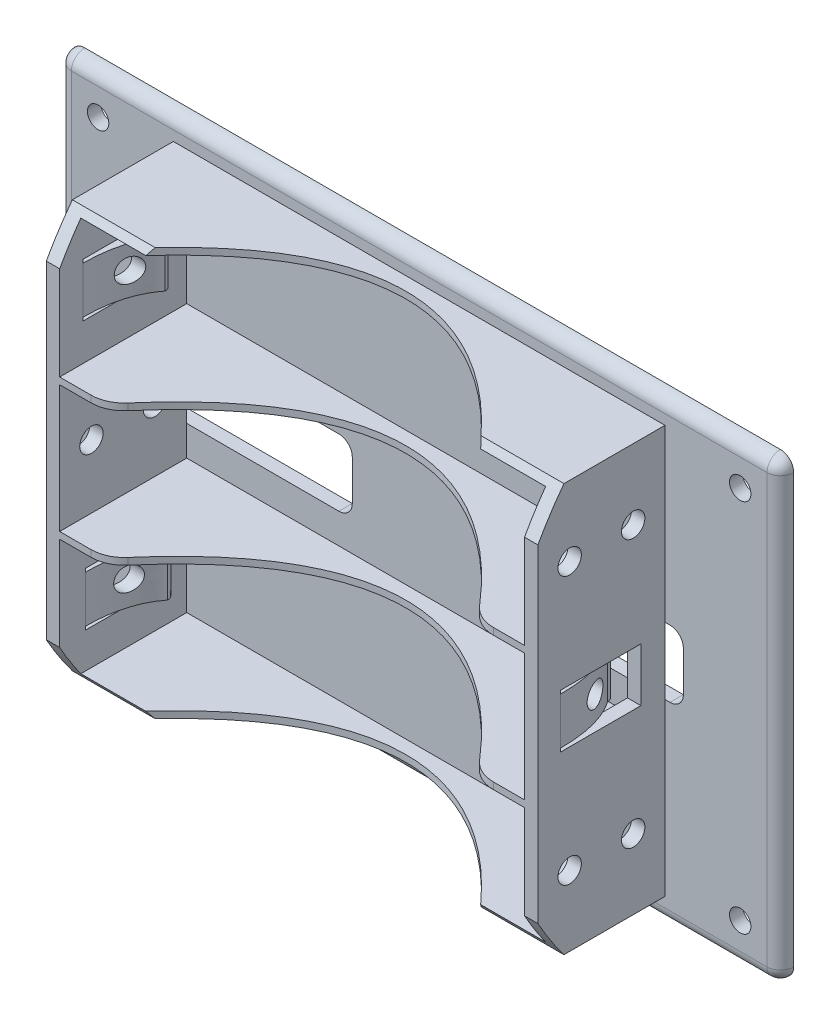
SolidWorks part; units mm, degrees
ref_plane "Płaszczyzna przednia" through (0, 0, 0) normal (0, 0, 1) x (1, 0, 0)
ref_plane "Płaszczyzna górna" through (0, 0, 0) normal (0, 1, 0) x (1, 0, 0)
ref_plane "Płaszczyzna prawa" through (0, 0, 0) normal (1, 0, 0) x (0, 0, -1)
sketch "Szkic1" plane through (0, 0, 0) normal (0, 0, 1) x (1, 0, 0)
  line L0 (-32.266, 2.8412) -> (-32.266, 0.8412) construction
  line L1 (-32.266, 0.8412) -> (-34.266, 0.8412) construction
  line L2 (71.734, 66.8412) -> (71.734, 68.8412) construction
  line L3 (71.734, 68.8412) -> (73.734, 68.8412) construction
  line L5 (73.734, 68.8412) -> (-34.266, 68.8412)
  line L6 (73.734, 68.8412) -> (73.734, 0.8412)
  line L7 (73.734, 0.8412) -> (-34.266, 0.8412)
  line L8 (-34.266, 68.8412) -> (-34.266, 0.8412)
extrude "Dodanie-wyciągnięcie1" add sketch "Szkic1" along normal blind 2
sketch "Szkic2" plane through (0, 0, 2) normal (0, 0, 1) x (1, 0, 0)
  line L0 (-34.266, 34.8412) -> (-15.016, 34.8412) construction
  line L1 (-34.266, 68.8412) -> (-34.266, 0.8412) construction
  line L2 (-15.016, 34.8412) -> (54.484, 34.8412) construction
  line L3 (54.484, 34.8412) -> (73.734, 34.8412) construction
  line L4 (73.734, 0.8412) -> (73.734, 68.8412) construction
  line L5 (-15.016, 34.8412) -> (-15.016, 25.3412)
  line L6 (-15.016, 25.3412) -> (-15.016, 24.3412)
  line L7 (-15.016, 24.3412) -> (-15.016, 5.3412)
  line L8 (-15.016, 5.3412) -> (-15.016, 4.3412)
  line L9 (-15.016, 34.8412) -> (-15.016, 44.3412)
  line L10 (-15.016, 44.3412) -> (-15.016, 45.3412)
  line L11 (-15.016, 45.3412) -> (-15.016, 64.3412)
  line L12 (54.484, 34.8412) -> (54.484, 44.3412)
  line L13 (-15.016, 64.3412) -> (-15.016, 65.3412)
  line L14 (54.484, 44.3412) -> (54.484, 45.3412)
  line L15 (54.484, 45.3412) -> (54.484, 64.3412)
  line L16 (54.484, 64.3412) -> (54.484, 65.3412)
  line L17 (54.484, 34.8412) -> (54.484, 25.3412)
  line L18 (54.484, 25.3412) -> (54.484, 24.3412)
  line L19 (54.484, 24.3412) -> (54.484, 5.3412)
  line L20 (54.484, 5.3412) -> (54.484, 4.3412)
  line L21 (-15.016, 25.3412) -> (54.484, 25.3412)
  line L22 (54.484, 44.3412) -> (-15.016, 44.3412)
  line L23 (-15.016, 24.3412) -> (54.484, 24.3412)
  line L24 (-15.016, 5.3412) -> (54.484, 5.3412)
  line L25 (-15.016, 45.3412) -> (54.484, 45.3412)
  line L26 (-15.016, 64.3412) -> (54.484, 64.3412)
  line L27 (-15.016, 65.3412) -> (54.484, 65.3412)
  line L28 (-15.016, 4.3412) -> (54.484, 4.3412)
  line L29 (-15.016, 4.3412) -> (-17.016, 4.3412)
  line L30 (-17.016, 4.3412) -> (-17.016, 65.3412)
  line L31 (-17.016, 65.3412) -> (-15.016, 65.3412)
  line L32 (54.484, 4.3412) -> (56.484, 4.3412)
  line L33 (56.484, 4.3412) -> (56.484, 65.3412)
  line L34 (56.484, 65.3412) -> (54.484, 65.3412)
  dimension "D1" = 61
  dimension "D2" = 2
  dimension "D3" = 2
  dimension "D4" = 61
extrude "Dodanie-wyciągnięcie2" add sketch "Szkic2" along normal blind 19 contours L31 L30 L29 L8 L7 L6 L5 L9 L10 L11 L13 | L33 L34 L16 L15 L14 L12 L17 L18 L19 L20 L32 | L25 L10 L22 L14 | L27 L13 L26 L16 | L6 L23 L18 L21 | L8 L28 L20 L24
sketch "Szkic4" plane through (-15.016, 0, 0) normal (1, 0, 0) x (0, 0, -1)
  line L0 (-2, 23.9412) -> (-20.2, 24.3412) construction
  line L1 (-2, 24.3412) -> (-2, 5.3412) construction
  line L2 (-21, 24.3412) -> (-2, 24.3412) construction
  line L4 (-2, 64.3412) -> (-21, 64.3412) construction
  line L5 (-21, 64.3412) -> (-2, 64.3412) construction
  line L6 (-2, 64.3412) -> (-2, 45.3412) construction
  line L7 (-20.2, 24.3412) -> (-20.2, 5.3412) construction
  line L8 (-21, 5.3412) -> (-2, 5.3412) construction
  line L9 (-21, 64.3412) -> (-21, 45.3412) construction
  line L10 (-21, 45.3412) -> (-2, 45.3412) construction
  line L11 (-21, 45.3412) -> (-2, 64.3412) construction
  line L12 (-20.2, 5.3412) -> (-2, 23.9412) construction
  line L14 (-5.5, 50.8412) -> (-17.5, 50.8412)
  line L15 (-5.5, 50.8412) -> (-5.5, 58.8412)
  line L16 (-5.5, 58.8412) -> (-17.5, 58.8412)
  line L17 (-17.5, 50.8412) -> (-17.5, 58.8412)
  line L18 (-5.5, 50.8412) -> (-17.5, 58.8412) construction
  line L19 (-5.5, 58.8412) -> (-17.5, 50.8412) construction
  line L20 (-5.1, 10.6412) -> (-17.1, 10.6412)
  line L21 (-5.1, 10.6412) -> (-5.1, 18.6412)
  line L22 (-5.1, 18.6412) -> (-17.1, 18.6412)
  line L23 (-17.1, 10.6412) -> (-17.1, 18.6412)
  line L24 (-5.1, 10.6412) -> (-17.1, 18.6412) construction
  line L25 (-5.1, 18.6412) -> (-17.1, 10.6412) construction
  point P6 (-11.5, 54.8412)
  point P23 (-11.1, 14.6412)
extrude "Wytnij-wyciągnięcie1" cut sketch "Szkic4" against normal blind 2
sketch "Szkic5" plane through (54.484, 0, 0) normal (-1, 0, 0) x (0, 0, 1)
  line L0 (2, 44.3412) -> (21.2, 44.3412) construction
  line L1 (21, 44.3412) -> (2, 44.3412) construction
  line L2 (2, 25.3412) -> (2, 44.3412) construction
  line L3 (21.2, 44.3412) -> (21.2, 25.3412) construction
  line L4 (21, 25.3412) -> (2, 25.3412) construction
  line L5 (21.2, 25.3412) -> (2, 44.3412) construction
  line L7 (5.6, 30.8412) -> (17.6, 30.8412)
  line L8 (5.6, 30.8412) -> (5.6, 38.8412)
  line L9 (5.6, 38.8412) -> (17.6, 38.8412)
  line L10 (17.6, 30.8412) -> (17.6, 38.8412)
  line L11 (5.6, 30.8412) -> (17.6, 38.8412) construction
  line L12 (5.6, 38.8412) -> (17.6, 30.8412) construction
  point P6 (11.6, 34.8412)
extrude "Wytnij-wyciągnięcie2" cut sketch "Szkic5" against normal blind 2
sketch "Szkic6" plane through (0, 58.8412, 0) normal (0, -1, 0) x (1, 0, 0)
  line L0 (-15.016, 5.5) -> (-14.516, 5.5) construction
  line L1 (-17.016, 5.5) -> (-15.016, 5.5) construction
  line L2 (-15.016, 5.5) -> (-15.016, 17.5) construction
  line L3 (-14.516, 5.5) -> (-14.516, 8) construction
  line L4 (-17.016, 11.5) -> (-15.016, 11.5) construction
  line L5 (-17.016, 5.5) -> (-17.016, 17.5) construction
  line L6 (-14.516, 8) -> (-12.266, 8)
  line L8 (-17.016, 17.5) -> (-15.016, 17.5) construction
  line L9 (-17.016, 17.5) -> (-17.016, 11.5) construction
  line L10 (-17.016, 11.5) -> (-14.516, 8) construction
  line L11 (-15.016, 17.5) -> (-15.016, 11.5) construction
  line L12 (-15.016, 11.5) -> (-12.266, 8) construction
  line L13 (-15.016, 17.5) -> (-17.016, 17.5)
  circle A0 centre (-13.391, 8) radius 1.125
  spline S0 degree 2 poles (-17.016, 17.5) (-17.016, 11.5) (-14.516, 8) knots 0 0 0 1 1 1
  spline S1 degree 2 poles (-15.016, 17.5) (-15.016, 11.5) (-12.266, 8) knots 0 0 0 1 1 1
  line M7 (-15.016, 5.5) -> (-15.016, 17.5)
  line M8 (-15.016, 17.5) -> (-17.016, 17.5)
  dimension "D1" = 2.25
extrude "Dodanie-wyciągnięcie3" add sketch "Szkic6" along normal blind 7 from offset 0.5 contours S0 M8 M7 | S1 S0 A0 M7 | S1 A0 L6 | L6 A0
sketch "Szkic7" plane through (0, 18.6412, 0) normal (0, -1, 0) x (1, 0, 0)
  line L0 (-15.016, 5.1) -> (-14.516, 5.1) construction
  line L1 (-14.516, 5.1) -> (-14.516, 7.6) construction
  line L2 (-14.516, 7.6) -> (-12.266, 7.6)
  line L3 (-15.016, 5.1) -> (-15.016, 17.1) construction
  line L4 (-12.266, 7.6) -> (-15.016, 11.1) construction
  line L6 (-15.016, 11.1) -> (-15.016, 17.1) construction
  line L7 (-17.016, 17.1) -> (-15.016, 17.1) construction
  line L8 (-14.516, 7.6) -> (-17.016, 11.1) construction
  line L9 (-17.016, 5.1) -> (-17.016, 17.1) construction
  line L10 (-17.016, 11.1) -> (-17.016, 17.1) construction
  line L11 (-15.016, 17.1) -> (-17.016, 17.1)
  circle A0 centre (-13.391, 7.6) radius 1.125
  spline S0 degree 2 poles (-12.266, 7.6) (-15.016, 11.1) (-15.016, 17.1) knots 0 0 0 1 1 1
  spline S1 degree 2 poles (-14.516, 7.6) (-17.016, 11.1) (-17.016, 17.1) knots 0 0 0 1 1 1
  line M5 (-15.016, 5.1) -> (-15.016, 17.1)
  line M6 (-15.016, 17.1) -> (-17.016, 17.1)
  dimension "D1" = 2.25
extrude "Dodanie-wyciągnięcie4" add sketch "Szkic7" along normal blind 7 from offset 0.5 contours L2 S0 A0 | L2 A0 | S1 A0 S0 M5 | S1 M5 M6
sketch "Szkic8" plane through (0, 30.8412, 0) normal (0, 1, 0) x (1, 0, 0)
  line L0 (54.484, -5.6) -> (53.984, -5.6) construction
  line L1 (53.984, -5.6) -> (53.984, -8.1) construction
  line L2 (53.984, -8.1) -> (51.734, -8.1)
  line L3 (56.484, -5.6) -> (56.484, -17.6) construction
  line L4 (56.484, -17.6) -> (56.484, -11.6) construction
  line L6 (56.484, -11.6) -> (53.984, -8.1) construction
  line L7 (54.484, -5.6) -> (54.484, -17.6) construction
  line L8 (54.484, -17.6) -> (54.484, -11.6) construction
  line L10 (54.484, -11.6) -> (51.734, -8.1) construction
  line L11 (54.484, -17.6) -> (56.484, -17.6)
  circle A0 centre (52.859, -8.1) radius 1.125
  spline S0 degree 2 poles (56.484, -17.6) (56.484, -11.6) (53.984, -8.1) knots 0 0 0 1 1 1
  spline S1 degree 2 poles (54.484, -17.6) (54.484, -11.6) (51.734, -8.1) knots 0 0 0 1 1 1
  line M9 (54.484, -5.6) -> (54.484, -17.6)
  line M10 (54.484, -17.6) -> (56.484, -17.6)
  dimension "D1" = 2.25
extrude "Dodanie-wyciągnięcie5" add sketch "Szkic8" along normal blind 7 from offset 0.5 contours S1 S0 A0 M9 | S0 M10 M9 | S1 A0 L2 | L2 A0
sketch "Szkic9" plane through (0, 65.3412, 0) normal (0, 1, 0) x (1, 0, 0)
  line L0 (56.484, -21) -> (47.484, -21) construction
  line L1 (56.484, -21) -> (56.484, -2) construction
  line L2 (-17.016, -21) -> (56.484, -21) construction
  line L3 (47.484, -21) -> (-8.016, -21)
  line L4 (-8.016, -21) -> (-17.016, -21) construction
  line L5 (-17.016, -21) -> (-17.016, -2) construction
  line L6 (56.484, -2) -> (-17.016, -2) construction
  line L7 (19.734, -21) -> (19.734, -2) construction
  line L8 (19.734, -2) -> (19.734, 13) construction
  line L9 (-17.016, -2) -> (56.484, -2) construction
  line L11 (47.484, -21) -> (19.734, 13) construction
  line L12 (19.734, 13) -> (-8.016, -21) construction
  spline S0 degree 2 poles (47.484, -21) (19.734, 13) (-8.016, -21) knots 0 0 0 1 1 1
extrude "Wytnij-wyciągnięcie3" cut sketch "Szkic9" against normal blind 67 contours L3 S0
fillet "Zaokrąglenie2" radius 5 8 edges at (47.484, 64.8412, 21) (-8.016, 64.8412, 21) (-8.016, 44.8412, 21) (47.484, 44.8412, 21) (-8.016, 24.8412, 21) (47.484, 24.8412, 21) (-8.016, 4.8412, 21) (47.484, 4.8412, 21)
sketch "Szkic10" plane through (54.484, 0, 0) normal (-1, 0, 0) x (0, 0, 1)
  line L0 (2, 24.3412) -> (21, 5.3412) construction
  line L1 (21, 24.3412) -> (2, 24.3412) construction
  line L2 (2, 5.3412) -> (2, 24.3412) construction
  line L3 (21, 5.3412) -> (21, 24.3412) construction
  line L4 (11.5, 54.8412) -> (2, 54.8412) construction
  line L6 (2, 64.3412) -> (21, 45.3412) construction
  line L7 (21, 64.3412) -> (2, 64.3412) construction
  line L8 (2, 45.3412) -> (2, 64.3412) construction
  line L9 (21, 45.3412) -> (21, 64.3412) construction
  line L10 (11.5, 54.8412) -> (21, 54.8412) construction
  line L11 (2, 14.8412) -> (11.5, 14.8412) construction
  line L12 (11.5, 14.8412) -> (21, 14.8412) construction
  line L13 (2, 44.3412) -> (21, 25.3412) construction
  line L14 (2, 25.3412) -> (2, 44.3412) construction
  circle A0 centre (6.75, 14.8412) radius 1.75
  circle A1 centre (16.25, 14.8412) radius 1.75
  circle A2 centre (6.75, 54.8412) radius 1.75
  circle A3 centre (16.25, 54.8412) radius 1.75
  circle A4 centre (11.5, 34.8412) radius 1.75
extrude "Wytnij-wyciągnięcie5" cut sketch "Szkic10" against normal blind 10 and the other way blind 10
sketch "Szkic11" plane through (-15.016, 0, 0) normal (1, 0, 0) x (0, 0, -1)
  line L0 (-21, 44.3412) -> (-2, 25.3412) construction
  line L1 (-21, 44.3412) -> (-21, 25.3412) construction
  line L2 (-2, 44.3412) -> (-2, 25.3412) construction
  line L3 (-11.5, 34.8412) -> (-2, 34.8412) construction
  line L4 (-11.5, 34.8412) -> (-21, 34.8412) construction
  line L5 (-21, 24.3412) -> (-2, 5.3412) construction
  line L6 (-21, 5.3412) -> (-2, 5.3412) construction
  line L7 (-2, 24.3412) -> (-2, 5.3412) construction
  line L8 (-21, 64.3412) -> (-2, 45.3412) construction
  line L9 (-21, 64.3412) -> (-21, 45.3412) construction
  line L10 (-21, 64.3412) -> (-2, 64.3412) construction
  line L11 (-2, 64.3412) -> (-2, 45.3412) construction
  circle A0 centre (-11.5, 54.8412) radius 1.75
  circle A1 centre (-11.5, 14.8412) radius 1.75
  circle A2 centre (-6.75, 34.8412) radius 1.75
  circle A3 centre (-16.25, 34.8412) radius 1.75
extrude "Wytnij-wyciągnięcie6" cut sketch "Szkic11" against normal blind 10 and the other way blind 10
sketch "Szkic13" plane through (0, 0, 0) normal (0, 0, -1) x (-1, 0, 0)
  line L0 (-73.734, 68.8412) -> (34.266, 0.8412) construction
  line L1 (-73.734, 68.8412) -> (34.266, 68.8412) construction
  line L2 (-73.734, 0.8412) -> (-73.734, 68.8412) construction
  line L3 (34.266, 68.8412) -> (34.266, 0.8412) construction
  line L4 (34.266, 68.8412) -> (-73.734, 0.8412) construction
  line L5 (34.266, 0.8412) -> (-73.734, 0.8412) construction
  line L6 (-61.734, 68.8412) -> (-61.734, 56.8412) construction
  line L7 (-59.234, 29.8412) -> (19.766, 29.8412)
  line L8 (-59.234, 29.8412) -> (-59.234, 39.8412)
  line L9 (-59.234, 39.8412) -> (19.766, 39.8412)
  line L10 (19.766, 29.8412) -> (19.766, 39.8412)
  line L11 (-59.234, 29.8412) -> (19.766, 39.8412) construction
  line L12 (-59.234, 39.8412) -> (19.766, 29.8412) construction
  line L17 (-61.734, 56.8412) -> (-73.734, 56.8412) construction
  line L18 (-61.734, 0.8412) -> (-61.734, 12.8412) construction
  line L19 (-61.734, 12.8412) -> (-73.734, 12.8412) construction
  line L20 (22.266, 0.8412) -> (22.266, 12.8412) construction
  line L21 (22.266, 12.8412) -> (34.266, 12.8412) construction
  line L22 (22.266, 68.8412) -> (22.266, 56.8412) construction
  line L23 (22.266, 56.8412) -> (34.266, 56.8412) construction
  line L24 (-61.734, 12.8412) -> (-73.734, 0.8412) construction
  line L25 (-61.734, 56.8412) -> (-73.734, 68.8412) construction
  line L26 (22.266, 56.8412) -> (34.266, 68.8412) construction
  line L27 (22.266, 12.8412) -> (34.266, 0.8412) construction
  line L29 (-29.734, 49.8412) -> (-9.734, 49.8412)
  line L30 (-29.734, 49.8412) -> (-29.734, 19.8412)
  line L31 (-29.734, 19.8412) -> (-9.734, 19.8412)
  line L32 (-9.734, 49.8412) -> (-9.734, 19.8412)
  line L33 (-29.734, 49.8412) -> (-9.734, 19.8412) construction
  line L34 (-29.734, 19.8412) -> (-9.734, 49.8412) construction
  circle A0 centre (28.266, 6.8412) radius 1.6
  circle A1 centre (28.266, 62.8412) radius 1.6
  circle A2 centre (-67.734, 62.8412) radius 1.6
  circle A3 centre (-67.734, 6.8412) radius 1.6
  point P36 (-19.734, 34.8412)
extrude "Wytnij-wyciągnięcie7" cut sketch "Szkic13" against normal blind 2 contours L30 L9 L8 L7 | L9 L32 L7 L10 | A2 | A3 | A0 | A1
fillet "Zaokrąglenie4" radius 2 12 edges at (-19.766, 39.8412, 1) (-19.766, 29.8412, 1) (59.234, 29.8412, 1) (59.234, 39.8412, 1) (19.734, 0.8412, 2) (-34.266, 34.8412, 2) (19.734, 68.8412, 2) (73.734, 34.8412, 2) (29.734, 29.8412, 1) (29.734, 39.8412, 1) (9.734, 39.8412, 1) (9.734, 29.8412, 1)
sketch "Szkic14" plane through (56.484, 0, 0) normal (1, 0, 0) x (0, 0, -1)
  line L1 (0, 66.8412) -> (-2, 66.8412) construction
  line L2 (-2, 2.8412) -> (-2, 66.8412) construction
  line L3 (0, 2.8412) -> (-2, 2.8412) construction
  line L4 (-32.4373, 66.8412) -> (-2, 66.8412)
  line L5 (-32.4373, 66.8412) -> (-32.4373, 2.8412)
  line L6 (-32.4373, 2.8412) -> (-2, 2.8412)
  line L7 (-2, 66.8412) -> (-2, 2.8412)
  circle A0 centre (23.15, 34.8412) radius 55
  circle A1 centre (23.15, 34.8412) radius 52.5
  circle A2 centre (23.15, 34.8412) radius 50.5
  line M15 (-2, 65.3412) -> (-21, 65.3412)
  line M16 (-21, 65.3412) -> (-21, 4.3412)
  line M17 (-21, 4.3412) -> (-2, 4.3412)
extrude "Wytnij-wyciągnięcie8" cut sketch "Szkic14" against normal up to vertex contours A2 A1 M15 M16 | A1 M15 M16 | A2 A1 M16 M17 | A1 M16 M17
